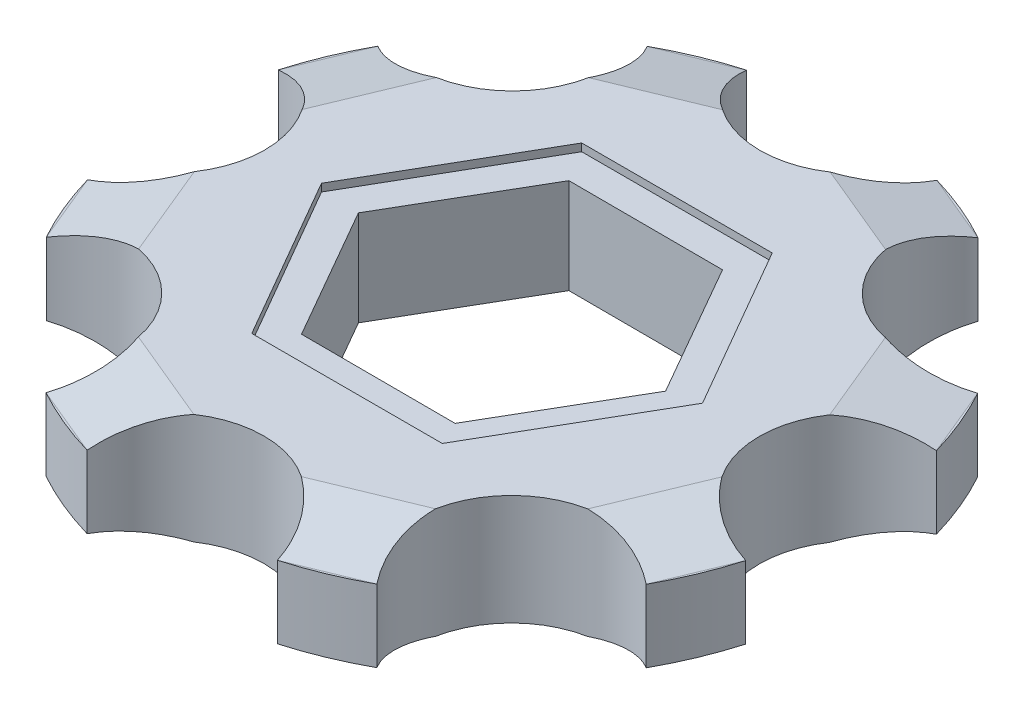
SolidWorks part; units mm, degrees
ref_plane "Front Plane" through (0, 0, 0) normal (0, 0, 1) x (1, 0, 0)
ref_plane "Top Plane" through (0, 0, 0) normal (0, 1, 0) x (1, 0, 0)
ref_plane "Right Plane" through (0, 0, 0) normal (1, 0, 0) x (0, 0, -1)
sketch "Sketch1" plane through (0, 0, 0) normal (0, 1, 0) x (1, 0, 0)
  circle A0 centre (0, 0) radius 9
extrude "Boss-Extrude2" add sketch "Sketch1" along normal blind 2.9 contours A0
ref_axis "Axis1" through (0, 2.9, 0) along (0, -1, 0)
sketch "Sketch3" plane through (0, 2.9, 0) normal (0, 1, 0) x (1, 0, 0)
  line L1 (2.03, 3.4947) -> (-2.0115, 3.5053)
  line L2 (-2.0115, 3.5053) -> (-4.0414, 0.0107)
  line L3 (-4.0414, 0.0107) -> (-2.03, -3.4947)
  line L4 (-2.03, -3.4947) -> (2.0115, -3.5053)
  line L5 (2.0115, -3.5053) -> (4.0414, -0.0107)
  line L6 (4.0414, -0.0107) -> (2.03, 3.4947)
  circle A0 centre (0, 0) radius 3.5 construction
  circle A1 centre (0, 0) radius 9 construction
  arc A2 (-2.4908, 8.6485) -> (2.5092, 8.6431) centre (0.0097, 9.0292) ccw
  arc A3 (4.3542, 7.8766) -> (7.8859, 4.3373) centre (6.3914, 6.3778) ccw
  arc A4 (8.6485, 2.4908) -> (8.6431, -2.5092) centre (9.0292, -0.0097) ccw
  arc A5 (7.8766, -4.3542) -> (4.3373, -7.8859) centre (6.3778, -6.3914) ccw
  arc A6 (2.4908, -8.6485) -> (-2.5092, -8.6431) centre (-0.0097, -9.0292) ccw
  arc A7 (-4.3542, -7.8766) -> (-7.8859, -4.3373) centre (-6.3914, -6.3778) ccw
  arc A8 (-8.6485, -2.4908) -> (-8.6431, 2.5092) centre (-9.0292, 0.0097) ccw
  arc A9 (-7.8766, 4.3542) -> (-4.3373, 7.8859) centre (-6.3778, 6.3914) ccw
  circle M11 centre (0, 0) radius 9
  dimension "D1" = 8
extrude "Cut-Extrude1" cut sketch "Sketch3" against normal through all contours A2 M11 | A3 M11 | A4 M11 | A5 M11 | A6 M11 | A7 M11 | A8 M11 | A9 M11 | L1 L2 L3 L4 L5 L6 region at (0.0084, 2.9, -7.8786) region at (-5.565, 2.9, -5.577) region at (5.577, 2.9, -5.565) region at (-7.8786, 2.9, -0.0084) region at (7.8786, 2.9, 0.0084) region at (-5.577, 2.9, 5.565) region at (5.565, 2.9, 5.577) region at (-0.0084, 2.9, 7.8786)
sketch "Sketch4" plane through (0, 2.9, 0) normal (0, 1, 0) x (1, 0, 0)
  line L0 (0, 0) -> (5, 0)
  line L2 (5, 0) -> (2.5, 4.3301)
  line L3 (2.5, 4.3301) -> (-2.5, 4.3301)
  line L4 (-2.5, 4.3301) -> (-5, 0)
  line L5 (-5, 0) -> (-2.5, -4.3301)
  line L6 (-2.5, -4.3301) -> (2.5, -4.3301)
  line L7 (2.5, -4.3301) -> (5, 0)
  circle A0 centre (0, 0) radius 4.3301 construction
extrude "Cut-Extrude2" cut sketch "Sketch4" against normal blind 0.2 contours L2 L3 L4 L5 L6 L7
ref_plane "Plane1" through (0, 1.45, 0) normal (0, 1, 0) x (1, 0, 0)
mirror "Mirror1" about plane through (0, 1.45, 0) normal (0, 1, 0) of "Cut-Extrude2"
ref_plane "Plane2" through (-8.2672, 0, 3.414) normal (-0.9243, 0, 0.3817) x (0.3817, 0, 0.9243)
sketch "Sketch7" plane through (-8.2672, 0, 3.414) normal (-0.9243, 0, 0.3817) x (0.3817, 0, 0.9243)
  line L0 (0, 0) -> (0, 0.5)
sketch "Sketch8" plane through (0, 0, 0) normal (0, -1, 0) x (1, 0, 0)
  line L1 (-8.2672, 3.414) -> (-6.4186, 2.6506)
ref_plane "Plane3" through (0, 0, 0) normal (-0.3817, 0, -0.9243) x (-0.9243, 0, 0.3817)
sketch "Sketch11" plane through (0, 0, 0) normal (-0.3817, 0, -0.9243) x (-0.9243, 0, 0.3817)
  line L0 (8.9444, 0.5) -> (6.9444, 0)
  line L1 (8.9444, 0) -> (8.9444, 0.5) construction
  line L3 (8.9444, 0.5) -> (8.9444, 0)
  line L4 (8.9444, 0) -> (6.9444, 0)
extrude "Cut-Extrude3" cut sketch "Sketch11" against normal blind 1.5 and the other way blind 1.5 contours L0 L4 L3
sketch "Sketch12" plane through (-8.2672, 0, 3.414) normal (-0.9243, 0, 0.3817) x (0.3817, 0, 0.9243)
  line L0 (-0.9989, 0.5) -> (-0.9989, 0)
  line L1 (-0.9989, 0) -> (0.9989, 0)
  line L2 (0.9989, 0) -> (0.9989, 0.5)
  line L3 (0.9989, 0.5) -> (-0.9989, 0.5)
extrude "Cut-Extrude6" cut sketch "Sketch12" along normal blind 1.5
mirror "Mirror4" about plane through (0, 1.45, 0) normal (0, 1, 0) of "Cut-Extrude3"
mirror "Mirror5" about plane through (0, 1.45, 0) normal (0, 1, 0) of "Cut-Extrude6"
pattern_circular "CirPattern1" count 8 over 360 about axis through (0, 2.9, 0) along (0, -1, 0) of "Cut-Extrude3", "Mirror5", "Mirror4", "Cut-Extrude6"
equation "\"0.8ftmm\"=0.2"
